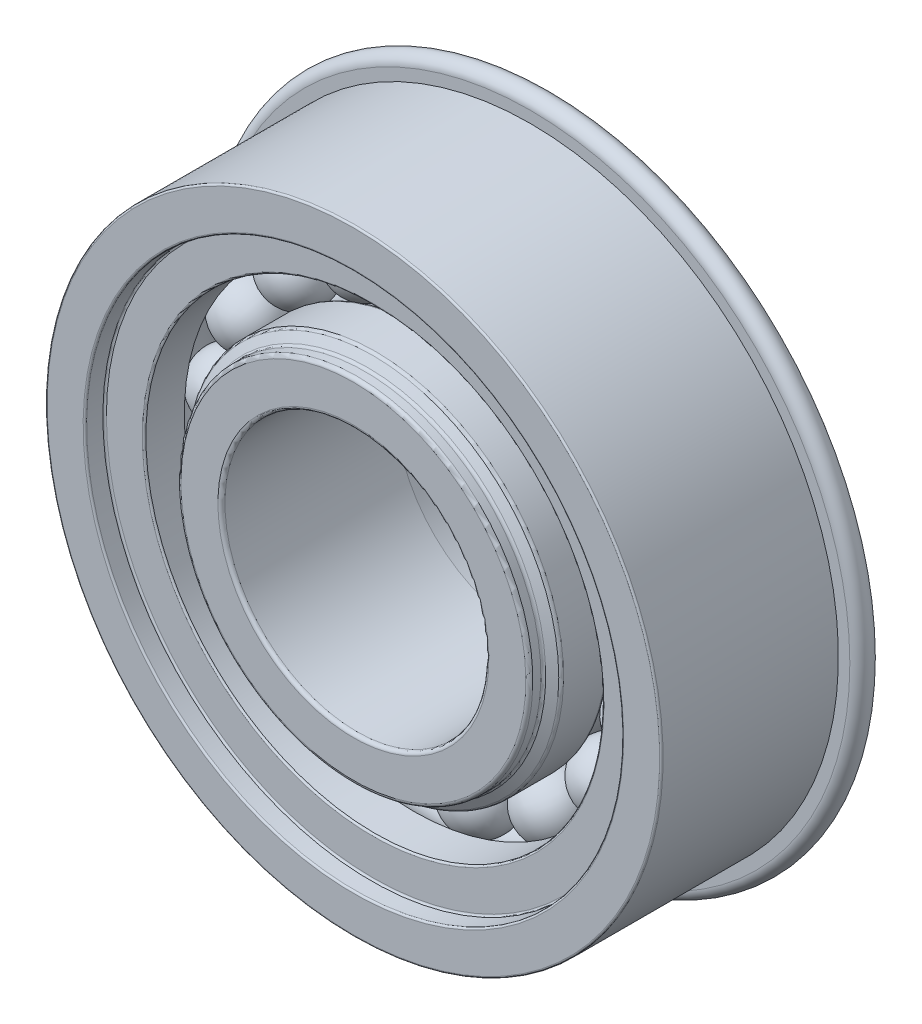
SolidWorks part; units mm, degrees
material "AISI 1020"
ref_plane "Front Plane" through (0, 0, 0) normal (0, 0, 1) x (1, 0, 0)
ref_plane "Top Plane" through (0, 0, 0) normal (0, 1, 0) x (1, 0, 0)
ref_plane "Right Plane" through (0, 0, 0) normal (1, 0, 0) x (0, 0, -1)
sketch "Sketch1" plane through (0, 0, 0) normal (1, 0, 0) x (0, 0, -1)
  line L0 (-7.9375, 0) -> (7.9375, 0) construction
  line L1 (6.3627, 0) -> (6.3627, 23.8125)
  line L2 (6.3627, 23.8125) -> (4.8387, 23.8125)
  line L3 (4.8387, 23.8125) -> (4.8387, 22.225)
  line L4 (4.8387, 22.225) -> (-7.9375, 22.225)
  line L5 (-7.9375, 9.525) -> (6.3627, 9.525)
  line L6 (-7.9375, 12.7) -> (7.9375, 12.7)
  line L7 (-1.5494, 22.225) -> (-1.5494, 17.4583) construction
  arc A0 (4.8387, 23.0505) -> (6.3627, 23.0505) centre (5.6007, 23.0505) cw
  point P4 (0, 0)
  dimension "Inner Ring Width" = 15.875
  dimension "Flange OD" = 47.625
  dimension "OD" = 44.45
  dimension "Width" = 14.3002
  dimension "ID" = 19.05
  dimension "Inner Ring OD" = 25.4
  dimension "Flange Thickness" = 1.524
  dimension "Ball Diameter" = 4.7667
  dimension "For Shaft Diameter" = 19.05
  dimension "For Housing ID" = 44.45
sketch "Sketch2" plane through (0, 0, 0) normal (1, 0, 0) x (0, 0, -1)
  line L0 (4.8387, 22.225) -> (-7.9375, 22.225) construction
  line L1 (4.8387, 22.225) -> (-7.9375, 22.225)
  line L2 (4.8387, 22.225) -> (4.8387, 23.0505)
  line L3 (6.3627, 23.0505) -> (6.3627, 16.5291)
  line L4 (6.3627, 0) -> (6.3627, 23.8125) construction
  line L5 (6.3627, 16.5291) -> (0.5147, 16.529)
  line L6 (-6.5135, 16.5291) -> (-6.5135, 19.377)
  line L7 (-6.5135, 19.377) -> (-7.9375, 19.377)
  line L8 (-7.9375, 19.377) -> (-7.9375, 22.225)
  line L9 (-1.5494, 17.7207) -> (-1.5494, 22.225) construction
  line L10 (-1.5494, 9.525) -> (-1.5494, 11.1125) construction
  line L11 (-1.5494, 11.1125) -> (-1.5494, 12.7) construction
  line L12 (-7.9375, 12.7) -> (7.9375, 12.7) construction
  line L13 (-7.9375, 9.525) -> (6.3627, 9.525) construction
  line L14 (-1.5494, 17.7207) -> (-1.5494, 16.5291) construction
  line L15 (-1.5494, 16.5291) -> (-1.5494, 15.3374) construction
  line L16 (-3.6135, 16.529) -> (-6.5135, 16.5291)
  line L17 (-5.0895, 19.377) -> (-7.9375, 19.377) construction
  arc A0 (6.3627, 23.0505) -> (4.8387, 23.0505) centre (5.6007, 23.0505) ccw construction
  arc A1 (6.3627, 23.0505) -> (4.8387, 23.0505) centre (5.6007, 23.0505) ccw
  circle A2 centre (-1.5494, 15.3374) radius 2.3834 construction
  arc A3 (-3.6135, 16.529) -> (0.5147, 16.529) centre (-1.5494, 15.3374) cw
  point P10 (-1.5494, 22.225)
  point P12 (-1.5494, 12.954)
  point P23 (-1.5494, 12.7)
  point P24 (-1.5494, 16.5291)
  point P33 (-6.5135, 19.377)
  dimension "D1" = 4.7667
  dimension "D2" = 0.254
revolve "Revolve1" add sketch "Sketch2" angle 360 about L0
sketch "Sketch3" plane through (0, 0, 0) normal (1, 0, 0) x (0, 0, -1)
  line L0 (-7.9375, 12.7) -> (7.9375, 12.7) construction
  line L1 (-7.9375, 12.7) -> (-6.9562, 12.7)
  line L2 (7.9375, 12.7) -> (7.9375, 9.525)
  line L3 (7.9375, 9.525) -> (-7.9375, 9.525)
  line L4 (-7.9375, 9.525) -> (-7.9375, 12.7)
  line L5 (4.8387, 12.7) -> (7.9375, 12.7)
  line L6 (-6.9562, 12.7) -> (-6.4655, 13.5498)
  line L7 (-6.4655, 13.5498) -> (-3.1258, 13.5498)
  line L8 (0.027, 13.5498) -> (4.348, 13.5498)
  line L9 (4.348, 13.5498) -> (4.8387, 12.7)
  line L10 (-1.5494, 15.3374) -> (-1.5494, 14.1457) construction
  line L11 (-1.5494, 14.1457) -> (-1.5494, 12.954) construction
  circle A2 centre (-1.5494, 15.3374) radius 2.3834 construction
  arc A3 (-3.1258, 13.5498) -> (0.027, 13.5498) centre (-1.5494, 15.3374) ccw
  point P12 (-1.5494, 13.5498)
  dimension "D1" = 60
  dimension "D2" = 60
revolve "Revolve2" add sketch "Sketch3" angle 360 about L0
sketch "Sketch5" plane through (0, 0, 0) normal (1, 0, 0) x (0, 0, -1)
  line L0 (7.9375, 10.3188) -> (7.9375, 9.525)
  line L2 (7.2679, 9.7569) -> (4.6176, 9.525)
  line L8 (7.6922, 10.3845) -> (7.9375, 10.3188) construction
  line L12 (7.9375, 12.7) -> (7.9375, 9.525) construction
  line L13 (7.9375, 10.3188) -> (7.9375, 11.1125) construction
  line L14 (7.9375, 9.525) -> (-7.9375, 9.525) construction
  line L15 (4.6176, 9.525) -> (7.9375, 9.525)
  arc A0 (7.9375, 10.3188) -> (7.2679, 9.7569) centre (7.2015, 10.516) cw
  dimension "D3" = 0.762
  dimension "D1" = 105
  dimension "D2" = 0.254
  dimension "D4" = 5
revolve "Cut-Revolve2" cut sketch "Sketch5" angle 360 about L0
sketch "Sketch6" plane through (0, 0, 0) normal (1, 0, 0) x (0, 0, -1)
  line L0 (7.6922, 10.3845) -> (7.9375, 10.3188) construction
  line L1 (7.6922, 10.3845) -> (7.9375, 10.3188)
  line L2 (7.6922, 10.3845) -> (7.9375, 11.3001) construction
  line L3 (7.9375, 12.7) -> (7.9375, 9.525) construction
  line L4 (7.9375, 11.3001) -> (7.9375, 10.3188) construction
  line L5 (7.2457, 10.0099) -> (6.3627, 9.9326)
  line L6 (6.3627, 0) -> (6.3627, 23.8125) construction
  line L7 (7.2679, 9.7569) -> (4.6176, 9.525) construction
  line L8 (6.3627, 9.9326) -> (6.3627, 10.0601)
  line L9 (7.5695, 10.4174) -> (7.9375, 10.4174)
  line L10 (7.2347, 10.1364) -> (6.3627, 10.0601)
  line L11 (7.9375, 10.4174) -> (7.9375, 10.3188)
  arc A1 (7.6922, 10.3845) -> (7.2457, 10.0099) centre (7.2015, 10.516) cw
  arc A2 (7.2347, 10.1364) -> (7.5695, 10.4174) centre (7.2015, 10.516) ccw
  arc A3 (7.2679, 9.7569) -> (7.9375, 10.3188) centre (7.2015, 10.516) ccw construction
  dimension "D1" = 0.127
revolve "Cut-Revolve3" cut sketch "Sketch6" angle 360 about L0
fillet "Fillet4" radius 0.762 1 edges at (0, -10.4174, -7.9375)
sketch "Sketch7" plane through (0, 0, 0) normal (1, 0, 0) x (0, 0, -1)
  line L0 (7.9375, 11.1125) -> (7.9375, 11.9062) construction
  line L1 (7.9375, 12.7) -> (7.9375, 9.525) construction
  line L2 (7.9375, 11.9062) -> (7.9375, 12.7) construction
  line L3 (7.9375, 11.9062) -> (7.9375, 12.7)
  line L4 (7.9375, 12.7) -> (7.6729, 12.7)
  line L5 (-7.9375, 12.7) -> (7.9375, 12.7) construction
  line L6 (7.6729, 12.7) -> (7.6729, 12.4354)
  line L7 (7.6729, 12.4354) -> (7.6729, 12.1708)
  line L8 (7.6729, 12.1708) -> (7.6729, 11.9062)
  line L9 (7.6729, 11.9062) -> (7.9375, 11.9062)
revolve "Cut-Revolve4" cut sketch "Sketch7" angle 360 about L0
sketch "Sketch11" plane through (0, 0, 0) normal (1, 0, 0) x (0, 0, -1)
  line L0 (-1.5494, 17.7207) -> (-1.5494, 12.954)
  circle A0 centre (-1.5494, 15.3374) radius 2.3834 construction
  arc A1 (-1.5494, 12.954) -> (-1.5494, 17.7207) centre (-1.5494, 15.3374) ccw
revolve "Revolve3" add sketch "Sketch11" angle 360 about L0
pattern_circular "CirPattern3" count 17 over 360 about axis through (0, 0, 7.9375) along (0, 0, -1) of bodies 111
fillet "Fillet2" radius 0.127 2 edges at (0, -19.377, 6.5135) (0, -16.5291, 6.5135)
fillet "Fillet3" radius 0.127 2 edges at (0, -22.225, 7.9375) (0, -19.377, 7.9375)
fillet "Fillet5" radius 0.254 9 edges at (0, -12.7, -7.6729) (0, -12.7, -4.8387) (0, -13.5498, -0.027) (0, -13.5498, 3.1258) (0, -13.5498, 6.4655) (0, -12.7, 6.9562) (0, -12.7, 7.9375) (0, -9.525, 7.9375) (0, -11.9062, -7.9375)
sketch "Sketch12" plane through (0, 0, -6.3627) normal (0, 0, -1) x (-1, 0, 0)
  line L0 (0, 16.529) -> (0, 23.0505) construction
  circle A0 centre (0, 0) radius 16.529 construction
  circle A1 centre (0, 0) radius 16.529
  circle A2 centre (0, 0) radius 23.0505 construction
  circle A3 centre (0, 0) radius 19.7898
  point P8 (0, 19.7898)
extrude "Cut-Extrude1" cut sketch "Sketch12" against normal blind 1.143
sketch "Sketch13" plane through (0, 0, 0) normal (0, 0, 1) x (1, 0, 0)
  circle A0 centre (0, 0) radius 12.7
  circle A1 centre (0, 0) radius 23.8125
  circle A2 centre (0, 0) radius 22.225
  circle A3 centre (0, 0) radius 9.525
  point P0 (0, 12.7)
  point P5 (0, 23.8125)
  point P8 (0, 22.225)
  point P11 (0, 9.525)
equation "\"D1@Sketch2\"=\"Ball Diameter@Sketch1\""
equation "\"D1@Cut-Extrude1\"=\"Flange Thickness@Sketch1\"*.75"
